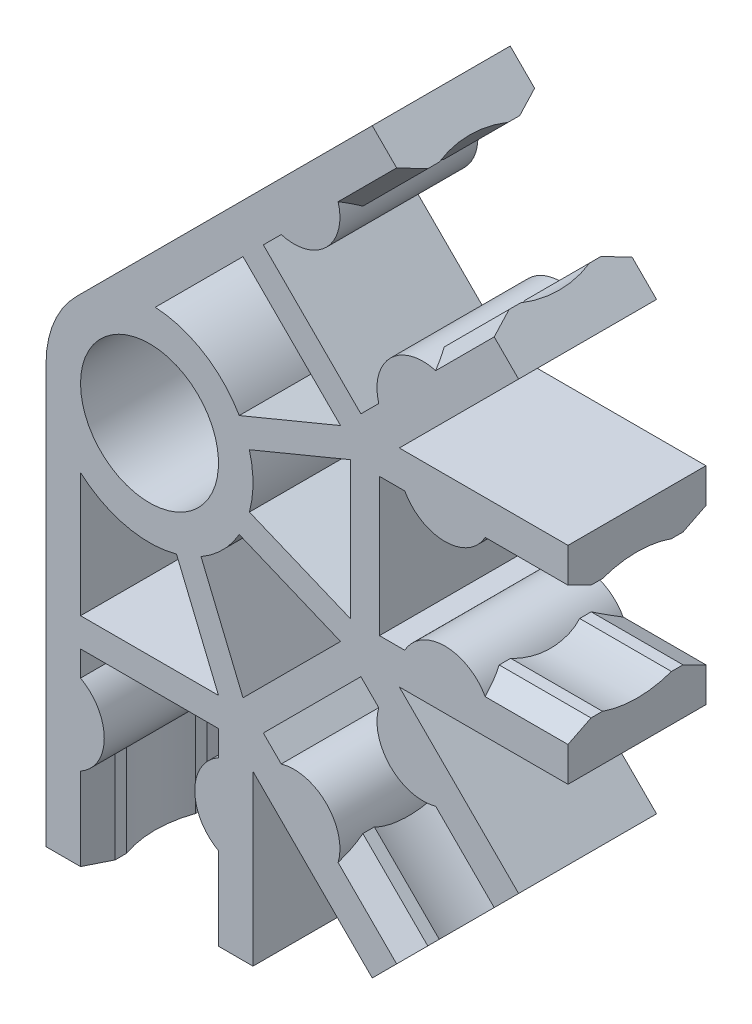
SolidWorks part; units mm, degrees
ref_plane "前视基准面" through (0, 0, 0) normal (0, 0, 1) x (1, 0, 0)
ref_plane "上视基准面" through (0, 0, 0) normal (0, 1, 0) x (1, 0, 0)
ref_plane "右视基准面" through (0, 0, 0) normal (1, 0, 0) x (0, 0, -1)
sketch "草图1" plane through (0, 0, 0) normal (0, 0, 1) x (1, 0, 0)
  line L0 (-4.5, 0) -> (-4.5, -18.2)
  line L1 (4.5, 0) -> (4.5, -18.2)
  line L2 (-4.5, -18.2) -> (-3, -18.2)
  line L3 (-3, -18.2) -> (-3, -14.6)
  line L4 (4.5, -18.2) -> (3, -18.2)
  line L5 (3, -18.2) -> (3, -14.6)
  line L6 (-3, -11.1) -> (-3, -10)
  line L7 (-3, -10) -> (3, -10)
  line L8 (3, -10) -> (3, -11.1)
  arc A0 (4.5, 0) -> (-4.5, 0) centre (0, 0) ccw
  arc A1 (-3, -11.1) -> (-3, -14.6) centre (-3.9682, -12.85) cw
  arc A2 (3, -11.1) -> (3, -14.6) centre (3.9682, -12.85) ccw
  point P1 (0, 4.5)
  dimension "D1" = 9
  dimension "D10" = 14.5
  dimension "D11" = 2
  dimension "D12" = 2
  dimension "D2" = 18.2
  dimension "D3" = 18.2
  dimension "D4" = 1.5
  dimension "D5" = 1.5
  dimension "D6" = 1.1
  dimension "D7" = 1.1
  dimension "D8" = 3.5
  dimension "D9" = 3.5
extrude "凸台-拉伸1" add sketch "草图1" along normal blind 6
sketch "草图3" plane through (0, -18.2, 0) normal (0, -1, 0) x (1, 0, 0)
  line L0 (-3, 6) -> (-3, 0)
  line L1 (-3, 0) -> (-2.5, 1)
  line L2 (-2.5, 1) -> (-2.5, 1.5)
  line L3 (-3, 6) -> (-2.5, 5)
  line L4 (-2.5, 5) -> (-2.5, 4.5)
  line L5 (0, 0) -> (0, 6.4845) construction
  line L6 (3, 0) -> (2.5, 1)
  line L7 (2.5, 1) -> (2.5, 1.5)
  line L8 (2.5, 5) -> (2.5, 4.5)
  line L9 (3, 6) -> (2.5, 5)
  line L10 (3, 6) -> (3, 0)
  arc A0 (-2.5, 1.5) -> (-2.5, 4.5) centre (1.7426, 3) cw
  arc A1 (2.5, 1.5) -> (2.5, 4.5) centre (-1.7426, 3) ccw
  dimension "D7" = 4.5
  dimension "D1" = 0.5
  dimension "D2" = 0.5
  dimension "D3" = 0.5
  dimension "D4" = 0.5
  dimension "D5" = 1.5
  dimension "D6" = 1.5
extrude "凸台-拉伸2" add sketch "草图3" against normal up to next
ref_axis "Axis" through (0, 0, 0) along (0, 0, 1)
pattern_circular "阵列(圆周)1" count 4 every 45 about axis through (0, 0, 0) along (0, 0, 1) of "凸台-拉伸1", "凸台-拉伸2"
sketch "草图4" plane through (0, 0, 0) normal (0, 0, -1) x (-1, 0, 0)
  line L0 (0, 0) -> (-10.864, -4.5) construction
  line L1 (3, -8.75) -> (3, -3.3541)
  line L2 (-3, -8.75) -> (3, -8.75)
  line L3 (-3, -8.75) -> (-1.1749, -4.3439)
  line L4 (-8.3085, -4.0659) -> (-4.0659, -8.3085)
  line L5 (-8.3085, -4.0659) -> (-3.9024, -2.2408)
  line L6 (-4.0659, -8.3085) -> (-2.2408, -3.9024)
  line L7 (0, 0) -> (-4.5, -10.864) construction
  line L8 (3, -10) -> (-3, -10) construction
  line L9 (-4.9497, -9.1924) -> (-9.1924, -4.9497) construction
  line L10 (0, 0) -> (-7.0711, -7.0711) construction
  line L11 (-8.75, -3) -> (-4.3439, -1.1749)
  line L12 (-8.75, -3) -> (-8.75, 3)
  line L13 (-8.75, 3) -> (-4.3439, 1.1749)
  line L14 (-4.0659, 8.3085) -> (-0.2504, 4.493)
  line L15 (-8.3085, 4.0659) -> (-4.0659, 8.3085)
  line L16 (-8.3085, 4.0659) -> (-3.9024, 2.2408)
  circle A0 centre (0, 0) radius 3
  arc A1 (-4.3439, 1.1749) -> (-4.3439, -1.1749) centre (0, 0) ccw
  arc A2 (-3.9024, -2.2408) -> (-2.2408, -3.9024) centre (0, 0) ccw
  arc A3 (-0.2504, 4.493) -> (-3.9024, 2.2408) centre (0, 0) ccw
  arc A4 (-1.1749, -4.3439) -> (3, -3.3541) centre (0, 0) ccw
  point P7 (-6.1872, -6.1872)
  dimension "D1" = 9
  dimension "D2" = 6
  dimension "D3" = 1.25
  dimension "D4" = 1.25
  dimension "D5" = 6
  dimension "D6" = 6
extrude "切除-拉伸1" cut sketch "草图4" against normal through all
